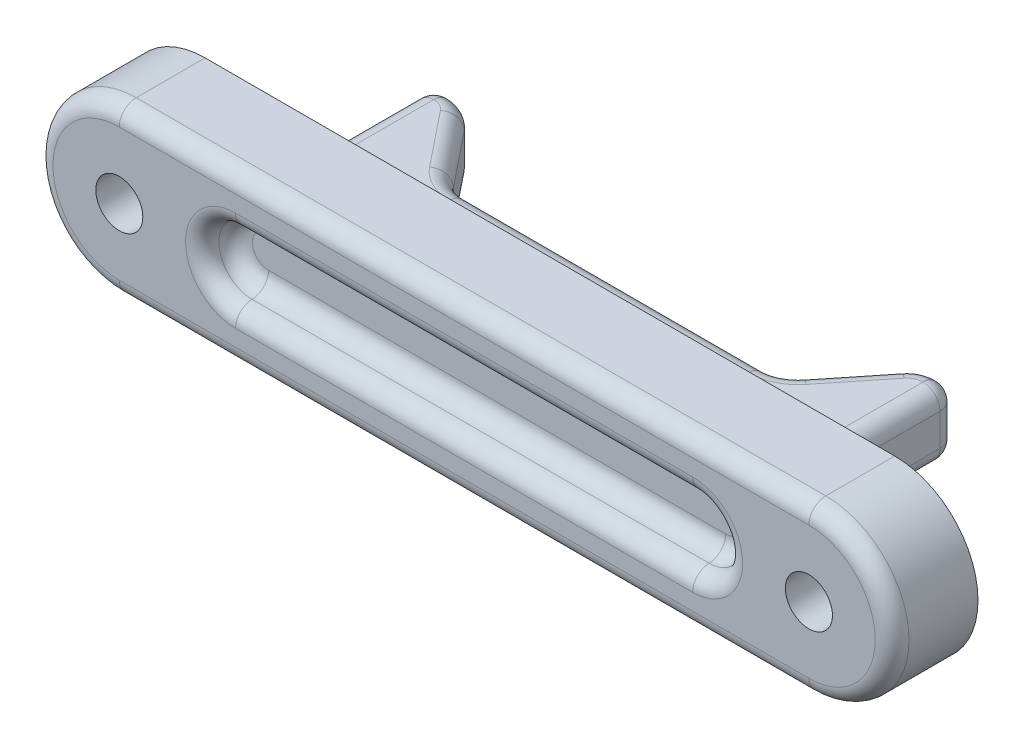
SolidWorks part; units mm, degrees
material "6061-T6 (SS)"
ref_plane "Front Plane" through (0, 0, 0) normal (0, 0, 1) x (1, 0, 0)
ref_plane "Top Plane" through (0, 0, 0) normal (0, 1, 0) x (1, 0, 0)
ref_plane "Right Plane" through (0, 0, 0) normal (1, 0, 0) x (0, 0, -1)
sketch "Sketch1" plane through (0, 0, 0) normal (0, 0, 1) x (1, 0, 0)
  line L1 (-16.5735, 4.0005) -> (16.5735, 4.0005)
  line L2 (-16.5735, 4.0005) -> (-16.5735, -4.0005) construction
  line L3 (-16.5735, -4.0005) -> (16.5735, -4.0005)
  line L4 (16.5735, 4.0005) -> (16.5735, -4.0005) construction
  line L5 (-16.5735, 4.0005) -> (16.5735, -4.0005) construction
  line L6 (-16.5735, -4.0005) -> (16.5735, 4.0005) construction
  arc A0 (-16.5735, 4.0005) -> (-16.5735, -4.0005) centre (-16.5735, 0) ccw
  arc A1 (16.5735, 4.0005) -> (16.5735, -4.0005) centre (16.5735, 0) cw
  point P0 (0, 0)
  dimension "D3" = 4.0005
  dimension "D4" = 4.0005
  dimension "D1" = 33.147
  dimension "D2" = 8.001
extrude "Boss-Extrude1" add sketch "Sketch1" along normal blind 4.1275
sketch "Sketch2" plane through (0, 0, 4.1275) normal (0, 0, 1) x (1, 0, 0)
  line L1 (-10.9855, 1.5875) -> (10.9855, 1.5875)
  line L2 (-10.9855, 1.5875) -> (-10.9855, -1.5875) construction
  line L3 (-10.9855, -1.5875) -> (10.9855, -1.5875)
  line L4 (10.9855, 1.5875) -> (10.9855, -1.5875) construction
  line L5 (-10.9855, 1.5875) -> (10.9855, -1.5875) construction
  line L6 (-10.9855, -1.5875) -> (10.9855, 1.5875) construction
  arc A0 (-10.9855, 1.5875) -> (-10.9855, -1.5875) centre (-10.9855, 0) ccw
  arc A2 (10.9855, 1.5875) -> (10.9855, -1.5875) centre (10.9855, 0) cw
  point P0 (0, 0)
  dimension "D3" = 1.5875
  dimension "D4" = 1.5875
  dimension "D1" = 21.971
  dimension "D2" = 3.175
extrude "Cut-Extrude1" cut sketch "Sketch2" against normal blind 1.5875
hole_wizard "#4-40 Tapped Hole1" positions "Sketch3" profile "Sketch4" tap size "#4-40" standard "ANSI Inch" end condition through all
sketch "Sketch3" plane through (0, 0, 4.1275) normal (0, 0, 1) x (1, 0, 0)
  point P0 (-16.5735, 0)
  point P3 (16.5735, 0)
sketch "Sketch4" plane through (-16.5735, 0, 4.1275) normal (1, 0, 0) x (0, -1, 0)
  line L0 (0, 0) -> (0, 4.1275)
  line L1 (0, 4.1275) -> (1.1303, 4.1275)
  line L2 (1.1303, 4.1275) -> (1.1303, 0)
  line L5 (1.1303, 0) -> (0, 0)
  line L11 (0, -6.35) -> (0, 107.95) construction
  dimension "Thru Tap Drill Dia." = 2.2606
  dimension "Thru Tap Drill Depth" = 4.1275
cosmetic thread "Hole Thread1" parameters "D2"=2.8448
cosmetic thread "Hole Thread2" parameters "D2"=2.8448
sketch "Sketch5" plane through (0, 0, 0) normal (0, 1, 0) x (1, 0, 0)
  line L0 (-17.7038, -4.1275) -> (-17.7038, 0)
  line L1 (-15.4432, 0) -> (-15.4432, -4.1275)
  line L2 (15.4432, -4.1275) -> (15.4432, 0)
  line L3 (17.7038, 0) -> (17.7038, -4.1275)
  line L4 (-12.573, -2.54) -> (12.573, -2.54)
  line L5 (-12.573, -4.1275) -> (-12.573, -2.54)
  line L6 (12.573, -2.54) -> (12.573, -4.1275)
  line L7 (-20.574, -4.1275) -> (-17.7038, -4.1275)
  line L8 (-15.4432, -4.1275) -> (-12.573, -4.1275)
  line L9 (12.573, -4.1275) -> (15.4432, -4.1275)
  line L10 (17.7038, -4.1275) -> (20.574, -4.1275)
  line L11 (-20.574, 0) -> (-20.574, -4.1275)
  line L12 (20.574, -4.1275) -> (20.574, 0)
  line L13 (-20.574, 0) -> (-17.7038, 0)
  line L14 (-15.4432, 0) -> (15.4432, 0)
  line L15 (17.7038, 0) -> (20.574, 0)
  line L16 (17.7038, 0) -> (20.574, 0) construction
  line L17 (-15.4432, 0) -> (15.4432, 0) construction
  line L18 (-20.574, 0) -> (-17.7038, 0) construction
  line L19 (20.574, -4.1275) -> (20.574, 0) construction
  line L20 (-20.574, 0) -> (-20.574, -4.1275) construction
  line L21 (17.7038, -4.1275) -> (20.574, -4.1275) construction
  line L22 (12.573, -4.1275) -> (15.4432, -4.1275) construction
  line L23 (-15.4432, -4.1275) -> (-12.573, -4.1275) construction
  line L24 (-20.574, -4.1275) -> (-17.7038, -4.1275) construction
  line L25 (12.573, -2.54) -> (12.573, -4.1275) construction
  line L26 (-12.573, -4.1275) -> (-12.573, -2.54) construction
  line L27 (-12.573, -2.54) -> (12.573, -2.54) construction
  line L28 (17.7038, 0) -> (17.7038, -4.1275) construction
  line L29 (15.4432, -4.1275) -> (15.4432, 0) construction
  line L30 (-15.4432, 0) -> (-15.4432, -4.1275) construction
  line L31 (-17.7038, -4.1275) -> (-17.7038, 0) construction
  line L32 (-12.573, 0) -> (-12.573, 6.985)
  line L33 (-12.573, 6.985) -> (-10.9855, 6.985)
  line L34 (-10.9855, 6.985) -> (-7.9375, 3.175)
  line L35 (-7.9375, 3.175) -> (7.9375, 3.175)
  line L36 (0, -1000) -> (0, 49000) construction
  line L37 (10.9855, 6.985) -> (7.9375, 3.175)
  line L38 (12.573, 6.985) -> (10.9855, 6.985)
  line L39 (12.573, 0) -> (12.573, 6.985)
  line L40 (-12.573, 0) -> (12.573, 0)
  point P18 (0, 3.175)
  dimension "D1" = 6.985
  dimension "D2" = 1.5875
  dimension "D3" = 8.001
  dimension "D4" = 15.875
  dimension "D5" = 3.175
extrude "Boss-Extrude2" add sketch "Sketch5" along normal mid plane 3.175
fillet "Fillet1" radius 1.5875 4 edges at (-10.9855, 0, -6.985) (10.9855, 0, -6.985) (7.9375, 0, -3.175) (-7.9375, 0, -3.175)
fillet "Fillet2" radius 0.8128 4 edges at (12.573, -1.5875, -3.4925) (12.573, 1.5875, -3.4925) (-12.573, -1.5875, -3.4925) (-12.573, 1.5875, -3.4925)
fillet "Fillet3" radius 0.8128 40 edges at (0, -1.5875, 4.1275) (-12.573, 0, 4.1275) (0, 1.5875, 4.1275) (-20.574, 0, 4.1275) (0, 4.0005, 4.1275) (20.574, 0, 4.1275) (7.8622, 1.5875, -3.3317) (9.4615, 1.5875, -5.08) (11.0608, 1.5875, -6.8283) (11.7543, 1.5875, -6.985) (12.3349, 1.3494, -6.985) (12.573, 0, -6.985) (12.3349, -1.3494, -6.985) (11.7543, -1.5875, -6.985) (11.0608, -1.5875, -6.8283) (9.4615, -1.5875, -5.08) (7.8622, -1.5875, -3.3317) (0, -1.5875, -3.175) (-7.8622, -1.5875, -3.3317) (-9.4615, -1.5875, -5.08) (-11.0608, -1.5875, -6.8283) (-11.7543, -1.5875, -6.985) (-12.3349, -1.3494, -6.985) (-12.573, 0, -6.985) (-12.3349, 1.3494, -6.985) (-11.7543, 1.5875, -6.985) (-11.0608, 1.5875, -6.8283) (-9.4615, 1.5875, -5.08) (-7.8622, 1.5875, -3.3317) (12.3349, 1.3494, 0) (12.573, 0, 0) (12.3349, -1.3494, 0) (0, -1.5875, 0) (-12.3349, -1.3494, 0) (-12.573, 0, 0) (-12.3349, 1.3494, 0) (0, 1.5875, 0) (12.573, 0, 4.1275) (0, -4.0005, 4.1275) (0, 1.5875, -3.175)
fillet "Fillet4" radius 0.8128 4 edges at (0, -1.5875, 2.54) (-12.573, 0, 2.54) (0, 1.5875, 2.54) (12.573, 0, 2.54)
equation "\"D4@Sketch1\"=\"D3@Sketch1\""
